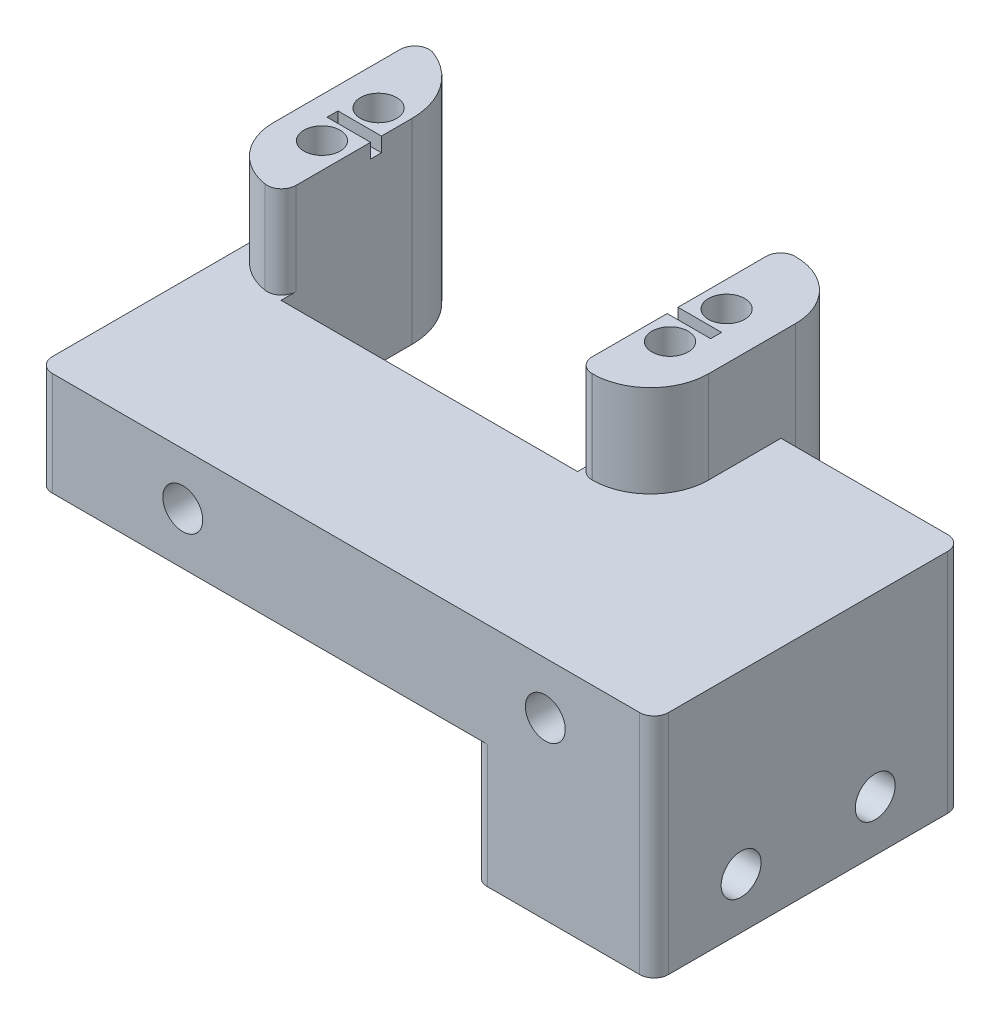
SolidWorks part; units mm, degrees
ref_plane "Front" through (0, 0, 0) normal (0, 0, 1) x (1, 0, 0)
ref_plane "Top" through (0, 0, 0) normal (0, 1, 0) x (1, 0, 0)
ref_plane "Right" through (0, 0, 0) normal (1, 0, 0) x (0, 0, -1)
sketch "Sketch1" plane through (0, 0, 0) normal (0, 1, 0) x (1, 0, 0)
  line L1 (0, 0) -> (85, 0)
  line L2 (0, 0) -> (0, 52.5)
  line L3 (0, 52.5) -> (85, 52.5)
  line L4 (85, 0) -> (85, 52.5)
  dimension "D1" = 85
  dimension "D2" = 52.5
extrude "Boss-Extrude1" add sketch "Sketch1" along normal blind 27
sketch "Sketch2" plane through (0, 27, 0) normal (0, 1, 0) x (1, 0, 0)
  line L0 (0, 52.5) -> (0, 0) construction
  line L1 (85, 52.5) -> (0, 52.5) construction
  circle A0 centre (5.5, 41.5) radius 2.5
  circle A1 centre (53.5, 41.5) radius 2.5
  circle A2 centre (53.5, 33.7) radius 2.5
  circle A3 centre (5.5, 33.7) radius 2.5
  dimension "D3" = 5
  dimension "D6" = 48
  dimension "D1" = 5.5
  dimension "D2" = 11
  dimension "D7" = 7.8
  dimension "D4" = 2
  dimension "D5" = 2
extrude "Cut-Extrude1" cut sketch "Sketch2" against normal through all
sketch "Sketch4" plane through (0, 0, 0) normal (-1, 0, 0) x (0, 0, 1)
  line L0 (-52.5, 27) -> (0, 27) construction
  line L1 (0, 27) -> (-24.5, 27)
  line L2 (0, 27) -> (0, 14.3)
  line L3 (0, 14.3) -> (-24.5, 14.3)
  line L4 (-24.5, 27) -> (-24.5, 14.3)
  line L5 (0, 27) -> (0, 0) construction
  dimension "D1" = 12.7
  dimension "D2" = 24.5
extrude "Cut-Extrude2" cut sketch "Sketch4" against normal through all
sketch "Sketch5" plane through (0, 0, -24.5) normal (0, 0, 1) x (1, 0, 0)
  line L0 (85, 14.3) -> (0, 14.3) construction
  line L1 (85, 27) -> (60, 27)
  line L2 (85, 27) -> (85, 14.3)
  line L3 (85, 14.3) -> (60, 14.3)
  line L4 (60, 27) -> (60, 14.3)
  dimension "D1" = 25
extrude "Cut-Extrude3" cut sketch "Sketch5" against normal through all
sketch "Sketch6" plane through (0, 27, 0) normal (0, 1, 0) x (1, 0, 0)
  line L0 (60, 24.5) -> (0, 24.5) construction
  line L1 (9.05, 24.5) -> (49.95, 24.5)
  line L2 (9.05, 24.5) -> (9.05, 52.5)
  line L3 (9.05, 52.5) -> (49.95, 52.5)
  line L4 (49.95, 24.5) -> (49.95, 52.5)
  line L5 (60, 52.5) -> (0, 52.5) construction
  line L6 (29.5, 41.5) -> (29.5, 52.5) construction
  line L7 (5.5, 41.5) -> (53.5, 41.5) construction
  circle A0 centre (5.5, 41.5) radius 2.5 construction
  dimension "D1" = 3.55
extrude "Cut-Extrude4" cut sketch "Sketch6" against normal through all
fillet "Fillet1" radius 10 1 edges at (9.05, 13.5, -52.5)
fillet "Fillet2" radius 8 3 edges at (60, 20.65, -52.5) (0, 20.65, -24.5) (60, 20.65, -24.5)
fillet "Fillet4" radius 2 7 edges at (9.05, 20.65, -24.5) (49.95, 20.65, -24.5) (49.95, 13.5, -52.5) (85, 7.15, -52.5) (85, 7.15, 0) (0, 7.15, 0) (0, 13.5, -52.5)
sketch "Sketch7" plane through (0, 0, 0) normal (0, 0, 1) x (1, 0, 0)
  line L0 (20, 0) -> (20, 14.3) construction
  line L1 (2, 0) -> (83, 0) construction
  line L2 (83, 14.3) -> (2, 14.3) construction
  line L3 (85, 14.3) -> (85, 0) construction
  circle A0 centre (70, 7.15) radius 2.75
  circle A1 centre (20, 7.15) radius 2.75
  dimension "D3" = 5.5
  dimension "D1" = 50
  dimension "D2" = 15
extrude "Cut-Extrude5" cut sketch "Sketch7" against normal through all
sketch "Sketch8" plane through (0, 27, 0) normal (0, 1, 0) x (1, 0, 0)
  line L0 (9.05, 42.5452) -> (9.05, 26.5757) construction
  line L1 (3.05, 38.35) -> (9.05, 38.35)
  line L2 (3.05, 38.35) -> (3.05, 36.85)
  line L3 (3.05, 36.85) -> (9.05, 36.85)
  line L4 (9.05, 38.35) -> (9.05, 36.85)
  line L5 (5.5, 39) -> (5.5, 36.2) construction
  line L6 (5.5, 37.6) -> (9.05, 37.6) construction
  line L7 (49.95, 26.5) -> (49.95, 50.5) construction
  line L8 (49.95, 36.85) -> (55.95, 36.85)
  line L9 (49.95, 36.85) -> (49.95, 38.35)
  line L10 (49.95, 38.35) -> (55.95, 38.35)
  line L11 (55.95, 36.85) -> (55.95, 38.35)
  circle A0 centre (5.5, 41.5) radius 2.5 construction
  circle A1 centre (5.5, 33.7) radius 2.5 construction
  dimension "D1" = 1.5
  dimension "D2" = 6
extrude "Cut-Extrude6" cut sketch "Sketch8" against normal blind 2
sketch "Sketch9" plane through (0, 14.3, 0) normal (0, 1, 0) x (1, 0, 0)
  line L0 (85, 50.5) -> (85, 2) construction
  line L1 (85, 42.5) -> (60, 42.5)
  line L2 (85, 42.5) -> (85, 52.5)
  line L3 (85, 52.5) -> (83, 52.5)
  line L4 (60, 42.5) -> (60, 44.5)
  line L5 (52, 52.5) -> (83, 52.5) construction
  line L6 (52, 52.5) -> (83, 52.5)
  arc A0 (60, 44.5) -> (52, 52.5) centre (52, 44.5) ccw construction
  arc A1 (60, 44.5) -> (52, 52.5) centre (52, 44.5) ccw
  point P6 (60.7979, 52.3027)
  point P7 (61.1036, 52.5)
  point P12 (82.7563, 52.5)
  dimension "D1" = 10
extrude "Cut-Extrude7" cut sketch "Sketch9" against normal through all
sketch "Sketch10" plane through (0, 0, 0) normal (0, -1, 0) x (1, 0, 0)
  line L0 (2, 0) -> (83, 0) construction
  line L1 (85, -42.5) -> (60, -42.5)
  line L2 (85, -42.5) -> (85, -2)
  line L3 (83, 0) -> (60, 0)
  line L4 (60, -42.5) -> (60, 0)
  line L5 (60, -44.5) -> (60, -42.5) construction
  arc A0 (85, -2) -> (83, 0) centre (83, -2) ccw
  dimension "D1" = 2
extrude "Boss-Extrude2" add sketch "Sketch10" along normal blind 17
sketch "Sketch11" plane through (85, 0, 0) normal (1, 0, 0) x (0, 0, -1)
  line L0 (42.5, -17) -> (42.5, 14.3) construction
  line L2 (0, -17) -> (0, 14.3) construction
  line L3 (42.5, -17) -> (2, -17) construction
  circle A0 centre (30.5, -10) radius 2.75
  circle A1 centre (12, -10) radius 2.75
  point P4 (0, 0)
  dimension "D4" = 5.5
  dimension "D1" = 12
  dimension "D2" = 12
  dimension "D3" = 7
extrude "Cut-Extrude8" cut sketch "Sketch11" against normal through all
fillet "Fillet5" radius 2 3 edges at (85, -1.35, -42.5) (60, -8.5, 0) (60, -8.5, -42.5)
